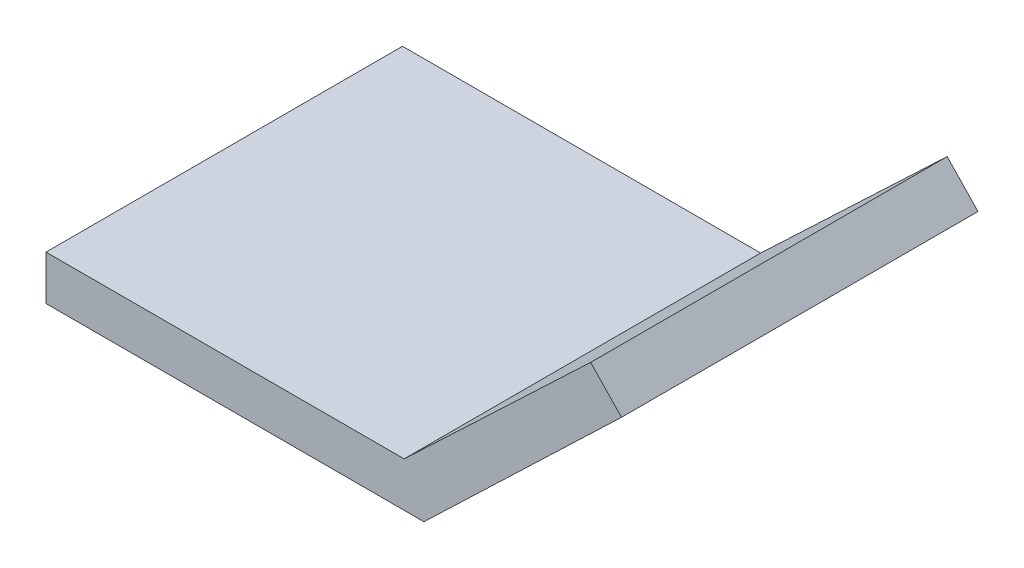
SolidWorks part; units mm, degrees
ref_plane "Front Plane" through (0, 0, 0) normal (0, 0, 1) x (1, 0, 0)
ref_plane "Top Plane" through (0, 0, 0) normal (0, 1, 0) x (1, 0, 0)
ref_plane "Right Plane" through (0, 0, 0) normal (1, 0, 0) x (0, 0, -1)
sketch "Sketch1" plane through (0, 0, 0) normal (0, 0, 1) x (1, 0, 0)
  line L0 (0, 0) -> (-26.924, 0)
  line L2 (-26.924, 0) -> (-26.924, 3.175)
  line L3 (-26.924, 3.175) -> (-1.408, 3.175)
  line L4 (-1.408, 3.175) -> (11.8816, 15.7734)
  line L5 (11.8816, 15.7734) -> (14.0775, 13.4802)
  line L6 (14.0775, 13.4802) -> (0, 0)
  dimension "D1" = 3.175
  dimension "D2" = 3.175
  dimension "D3" = 26.924
  dimension "D5" = 19.4908
other "AlignGroup1"
other "AlignGroup2"
extrude "Boss-Extrude1" add sketch "Sketch1" along normal blind 25.4
